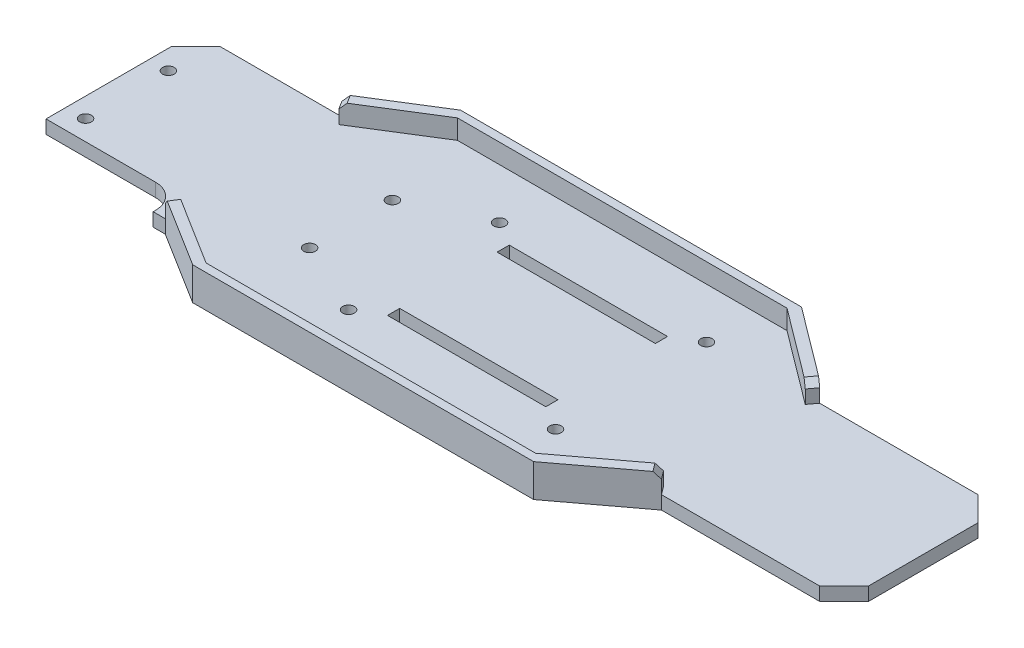
SolidWorks part; units mm, degrees
material "PETG - Polymaker"
ref_plane "Front Plane" through (0, 0, 0) normal (0, 0, 1) x (1, 0, 0)
ref_plane "Top Plane" through (0, 0, 0) normal (0, 1, 0) x (1, 0, 0)
ref_plane "Right Plane" through (0, 0, 0) normal (1, 0, 0) x (0, 0, -1)
sketch "Sketch1" plane through (0, 0, 0) normal (0, 1, 0) x (1, 0, 0)
  line L0 (-235.1499, 0) -> (235.1499, 0) construction
  line L1 (0, 0) -> (0, 52596.8311) construction
  line L2 (-100, 36.25) -> (-70, 55)
  line L3 (-70, 55) -> (70, 55)
  line L4 (-100, 36.25) -> (-160, 36.25)
  line L5 (-160, 36.25) -> (-160, -36.25)
  line L6 (-70, -55) -> (70, -55)
  line L7 (-100, -36.25) -> (-70, -55)
  line L8 (-100, -36.25) -> (-160, -36.25)
  line L9 (70, 55) -> (100, 32.5)
  line L10 (100, 32.5) -> (175, 32.5)
  line L11 (175, 32.5) -> (175, -32.5)
  line L12 (100, -32.5) -> (175, -32.5)
  line L13 (70, -55) -> (100, -32.5)
  point P3 (0, 0)
  point P10 (-85, 45.625)
  point P15 (-85, -45.625)
  point P18 (-160, 0)
  point P19 (0, -55)
  point P20 (0, 55)
  point P23 (175, 0)
  dimension "D1" = 55
  dimension "D2" = 72.5
  dimension "D3" = 30
  dimension "D4" = 60
  dimension "D5" = 140
  dimension "D6" = 75
  dimension "D7" = 65
  dimension "D8" = 30
  dimension "D9" = 110
extrude "Boss-Extrude1" add sketch "Sketch1" along normal blind 5.5
sketch "Sketch3" plane through (0, 5.5, 0) normal (0, 1, 0) x (1, 0, 0)
  line L0 (0, 0) -> (50000, 0) construction
  line L1 (0, 0) -> (0, 50000) construction
  line L2 (0, 55) -> (-70, 55)
  line L3 (70, 55) -> (-70, 55) construction
  line L4 (-70, 55) -> (-100, 36.25)
  line L5 (-100, 36.25) -> (-97.88, 32.858)
  line L6 (-97.88, 32.858) -> (-67.88, 51.608)
  line L7 (-67.88, 51.608) -> (0, 51.608)
  line L8 (-70, 55) -> (-67.88, 51.608) construction
  line L9 (0, 55) -> (70, 55)
  line L10 (70, 55) -> (100, 32.5)
  line L11 (100, 32.5) -> (97.456, 29.108)
  line L12 (97.456, 29.108) -> (67.456, 51.608)
  line L13 (67.456, 51.608) -> (0, 51.608)
  line L14 (67.456, 51.608) -> (70, 55) construction
  line L15 (67.456, -51.608) -> (70, -55) construction
  line L16 (-70, -55) -> (-67.88, -51.608) construction
  line L17 (67.456, -51.608) -> (0, -51.608)
  line L18 (97.456, -29.108) -> (67.456, -51.608)
  line L19 (100, -32.5) -> (97.456, -29.108)
  line L20 (70, -55) -> (100, -32.5)
  line L21 (0, -55) -> (70, -55)
  line L22 (-67.88, -51.608) -> (0, -51.608)
  line L23 (-97.88, -32.858) -> (-67.88, -51.608)
  line L24 (-100, -36.25) -> (-97.88, -32.858)
  line L25 (-70, -55) -> (-100, -36.25)
  line L26 (0, -55) -> (-70, -55)
  dimension "D1" = 4
extrude "Chassis-Walls1" add sketch "Sketch3" along normal blind 8
chamfer "Chamfer1" distance 10 angle 45 2 edges at (-160, 2.75, -36.25) (-160, 2.75, 36.25)
chamfer "Chamfer2" distance 10 angle 45 2 edges at (175, 2.75, -32.5) (175, 2.75, 32.5)
chamfer "Chamfer3" distance 2.5 angle 45 4 edges at (-98.94, 13.5, -34.554) (-98.94, 13.5, 34.554) (98.728, 13.5, 30.804) (98.728, 13.5, -30.804)
sketch "Sketch4" plane through (0, 0, 0) normal (0, -1, 0) x (1, 0, 0)
  line L0 (0, 0) -> (50000, 0) construction
  line L1 (-152, 17) -> (-60, 17) construction
  line L2 (-160, -26.25) -> (-160, 26.25) construction
  circle A0 centre (-152, 17) radius 2.4
  circle A1 centre (-60, 17) radius 2.4
  circle A2 centre (-60, -17) radius 2.4
  circle A3 centre (-152, -17) radius 2.4
  circle A4 centre (-30, 31) radius 2.4
  circle A5 centre (55, 31) radius 2.4
  circle A6 centre (55, -31) radius 2.4
  circle A7 centre (-30, -31) radius 2.4
  dimension "D1" = 4.8
  dimension "D2" = 4.8
  dimension "D6" = 4.8
  dimension "D8" = 4.8
  dimension "D3" = 8
  dimension "D4" = 92
  dimension "D5" = 34
  dimension "D7" = 30
  dimension "D9" = 85
  dimension "D10" = 62
extrude "Cut-Extrude1" cut sketch "Sketch4" against normal blind 10
sketch "Sketch5" plane through (0, 5.5, 0) normal (0, 1, 0) x (1, 0, 0)
  line L0 (-160, -25.25) -> (-105, -25.25)
  line L1 (-160, 26.25) -> (-160, -26.25) construction
  line L2 (-105, -25.25) -> (-105, -36.25)
  line L3 (-150, -36.25) -> (-100, -36.25) construction
  line L4 (-105, -36.25) -> (-160, -36.25)
  line L5 (-160, -36.25) -> (-160, -25.25)
  dimension "D1" = 55
  dimension "D2" = 11
extrude "Cut-Extrude2" cut sketch "Sketch5" against normal blind 10
sketch "Sketch6" plane through (0, 5.5, 0) normal (0, 1, 0) x (1, 0, 0)
  line L0 (0, 0) -> (50000, 0) construction
  line L1 (55, 31) -> (-30, 31) construction
  line L2 (12.5, 30.75) -> (12.5, 50030.75) construction
  line L3 (-20, -20) -> (45, -25) construction
  line L4 (-20, 25) -> (45, 25)
  line L5 (-20, 25) -> (-20, 20)
  line L6 (-20, 20) -> (45, 20)
  line L7 (45, 25) -> (45, 20)
  line L8 (-20, 25) -> (45, 20) construction
  line L9 (-20, 20) -> (45, 25) construction
  line L10 (-20, -25) -> (45, -20) construction
  line L11 (45, -25) -> (45, -20)
  line L12 (-20, -20) -> (45, -20)
  line L13 (-20, -25) -> (-20, -20)
  line L14 (-20, -25) -> (45, -25)
  point P9 (12.5, 31)
  point P10 (12.5, 22.5)
  point P19 (12.5, -22.5)
  dimension "D1" = 5
  dimension "D2" = 65
  dimension "D3" = 20
extrude "Cut-Extrude3" cut sketch "Sketch6" against normal through all
fillet "Fillet1" radius 10 1 edges at (-105, 2.75, 25.25)
equation "\"D6@Sketch4\"=\"D2@Sketch4\""
equation "\"D8@Sketch4\"=\"D2@Sketch4\""
